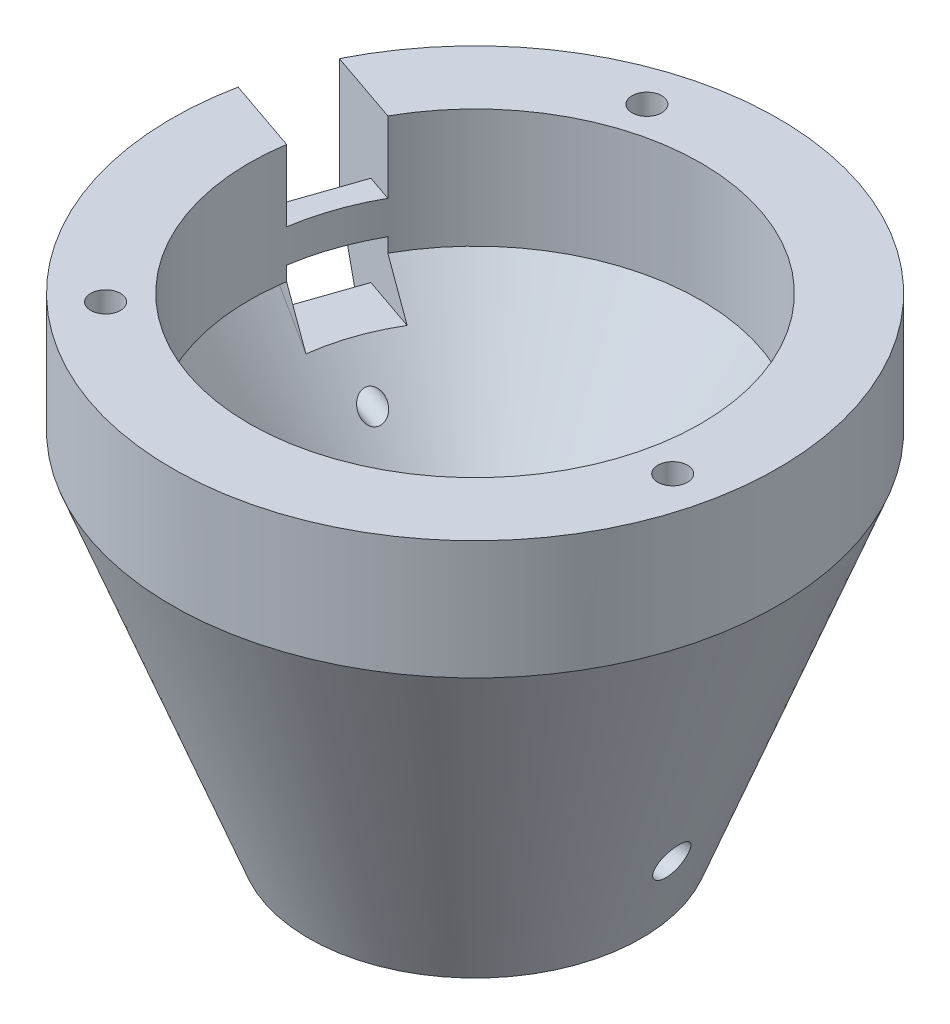
SolidWorks part; units mm, degrees
ref_plane "Front" through (0, 0, 0) normal (0, 0, 1) x (1, 0, 0)
ref_plane "Top" through (0, 0, 0) normal (0, 1, 0) x (1, 0, 0)
ref_plane "Right" through (0, 0, 0) normal (1, 0, 0) x (0, 0, -1)
sketch "Sketch1" plane through (0, 0, 0) normal (0, 0, 1) x (1, 0, 0)
  line L1 (9.3, 0) -> (9.3, 5)
  line L2 (19, 40) -> (25.5, 40)
  line L3 (9.3, 0) -> (14, 0)
  line L4 (25.5, 40) -> (25.5, 30)
  line L5 (25.5, 30) -> (14, 0)
  line L6 (19, 40) -> (19, 30)
  line L7 (19, 30) -> (9, 16)
  line L14 (9, 5) -> (9.3, 5)
  line L15 (9, 16) -> (9, 5)
  dimension "D1" = 14
  dimension "D2" = 25.5
  dimension "D3" = 16
  dimension "D4" = 40
  dimension "D5" = 19
  dimension "D6" = 10
  dimension "D7" = 10
  dimension "D8" = 9
  dimension "D9" = 5
  dimension "D12" = 9.3
sketch "Sketch2" plane through (0, 0, 0) normal (0, 0, 1) x (1, 0, 0)
  line L0 (0, 0) -> (0, 8.2423)
revolve "Revolve1" add sketch "Sketch1" angle 360 about L0
thread "Thread2" pitch 1.5 method extrude profile "Thread Profile4" start angle 0, offset 0, length 0, pitch 1.5, diameter 18
ref_plane "Plane4" through (9, 5, 0) normal (0, 0, 1) x (1, 0, 0)
sketch "Thread Profile4" plane through (9, 5, 0) normal (0, 0, 1) x (1, 0, 0)
  line L0 (0, 0) -> (0, 1.5) construction
  line L11 (0, 0) -> (0, 1.3125)
  line L12 (0, 1.3125) -> (-0.8119, 0.8437)
  line L13 (-0.8119, 0.8437) -> (-0.8119, 0.4687)
  line L15 (-0.8119, 0.4687) -> (0, 0)
  line L17 (-0.8119, 0.6562) -> (0, 0.6562) construction
  point P2 (0, 0)
  dimension "Pitch" = 1.5
  dimension "Profile_Angle" = 60
  dimension "Profile_Land" = 0.375
  dimension "Profile_Height" = 0.8119
hole_wizard "Ø2.5mm Dowel Hole1" positions "Sketch3" profile "Sketch5" hole size "Ø2.5" standard "DIN"
sketch "Sketch3" plane through (0, 40, 0) normal (0, 1, 0) x (1, 0, 0)
  circle A0 centre (0, 0) radius 25.5 construction
  point P0 (21.4625, -4.8335)
  dimension "D1" = 22
sketch "Sketch5" plane through (21.4625, 40, 4.8335) normal (1, 0, 0) x (0, 0, 1)
  line L0 (0, 0) -> (0, 10.7511)
  line L1 (0, 10.7511) -> (1.25, 10)
  line L2 (1.25, 10) -> (1.25, 0)
  line L5 (1.25, 0) -> (0, 0)
  line L10 (0, 10.7511) -> (-1.25, 10) construction
  line L11 (0, -6.35) -> (0, 107.95) construction
  dimension "Hole Dia." = 2.5
  dimension "Hole Depth" = 10
  dimension "Drill Angle" = 118
pattern_circular "CirPattern1" count 3 every 120 about axis through (0, 0, 0) along (0, 1, 0) of "Ø2.5mm Dowel Hole1"
hole_wizard "Ø3.0mm Dowel Hole1" positions "3DSketch2" profile "Sketch6" hole size "Ø3.0" standard "DIN" end condition through all
sketch3d "3DSketch2"
  point P0 (25.4998, 7, 0.1104)
  dimension "D1" = 33
sketch "Sketch6" plane through (25.4998, 7, 0.1104) normal (0, 1, 0) x (0.0043, 0, -1)
  line L0 (0, 0) -> (0, 51.1101)
  line L1 (0, 51.1101) -> (1.5, 51.1101)
  line L2 (1.5, 51.1101) -> (1.5, 0)
  line L5 (1.5, 0) -> (0, 0)
  line L11 (0, -6.35) -> (0, 107.95) construction
  dimension "Thru Hole Dia." = 3
  dimension "Thru Hole Depth" = 51.1101
sketch "Sketch8" plane through (-22.6934, 0, -7.8109) normal (-0.9456, 0, -0.3255) x (-0.3255, 0, 0.9456)
  line L0 (-3.35, 38.8) -> (3.35, 38.8)
  line L5 (3.35, 38.8) -> (3.35, 20.1)
  line L6 (-3.35, 20.1) -> (3.35, 20.1)
  line L7 (-3.35, 38.8) -> (-3.35, 20.1)
extrude "Cut-Extrude1" cut sketch "Sketch8" along normal through all
extrude "Cut-Extrude2" cut sketch "Sketch8<2>" against normal blind 3
sketch "Sketch8<2>" plane through (-22.6934, 0, -7.8109) normal (-0.9456, 0, -0.3255) x (-0.3255, 0, 0.9456) same geometry as "Sketch8"
sketch "Sketch9" plane through (-12.2923, 0, -4.2309) normal (0.9456, 0, 0.3255) x (0.3255, 0, -0.9456)
  line L11 (3.35, 37.6) -> (3.35, 34)
  line L12 (-3.35, 34) -> (3.35, 34)
  line L13 (-3.35, 37.6) -> (-3.35, 34)
  line L14 (-3.35, 38.8) -> (-3.35, 37.6)
  line L15 (3.35, 38.8) -> (-3.35, 38.8)
  line L16 (3.35, 37.6) -> (3.35, 38.8)
  line L17 (3.35, 26.4) -> (3.35, 31.2)
  line L18 (3.35, 31.2) -> (-3.35, 31.2)
  line L19 (-3.35, 26.4) -> (-3.35, 31.2)
  line L20 (3.35, 26.4) -> (-3.35, 26.4)
extrude "Cut-Extrude3" cut sketch "Sketch9" against normal through all
hole_wizard "Ø2.0 (2) Diameter Hole1" positions "Sketch10" profile "Sketch11" hole size "Ø2.0" standard "DIN" end condition up to next
sketch "Sketch10" plane through (-19.8567, 0, -6.8345) normal (-0.9456, 0, -0.3255) x (-0.3255, 0, 0.9456)
  point P0 (0, 22.9)
sketch "Sketch11" plane through (-19.8567, 22.9, -6.8345) normal (0, 1, 0) x (-0.3255, 0, 0.9456)
  line L0 (0, 0) -> (0, 7.0714)
  line L1 (0, 7.0714) -> (1, 7.0714)
  line L2 (1, 7.0714) -> (1, 0)
  line L5 (1, 0) -> (0, 0)
  line L11 (0, -6.35) -> (0, 107.95) construction
  dimension "Thru Hole Dia." = 2
  dimension "Thru Hole Depth" = 7.0714
sketch "Sketch12" plane through (0, 38.8, 0) normal (0, -1, 0) x (1, 0, 0)
  line L0 (-24.8196, -12.0856) -> (-16.5939, -9.2544)
  line L1 (-16.5939, -9.2544) -> (-18.7744, -2.9191)
  line L2 (-18.7744, -2.9191) -> (-27.0486, -5.7671)
  line L3 (-24.8196, -12.0856) -> (-27.0486, -5.7671)
  point P7 (-24.4096, -13.2477)
extrude "Cut-Extrude4" cut sketch "Sketch12" against normal blind 10
